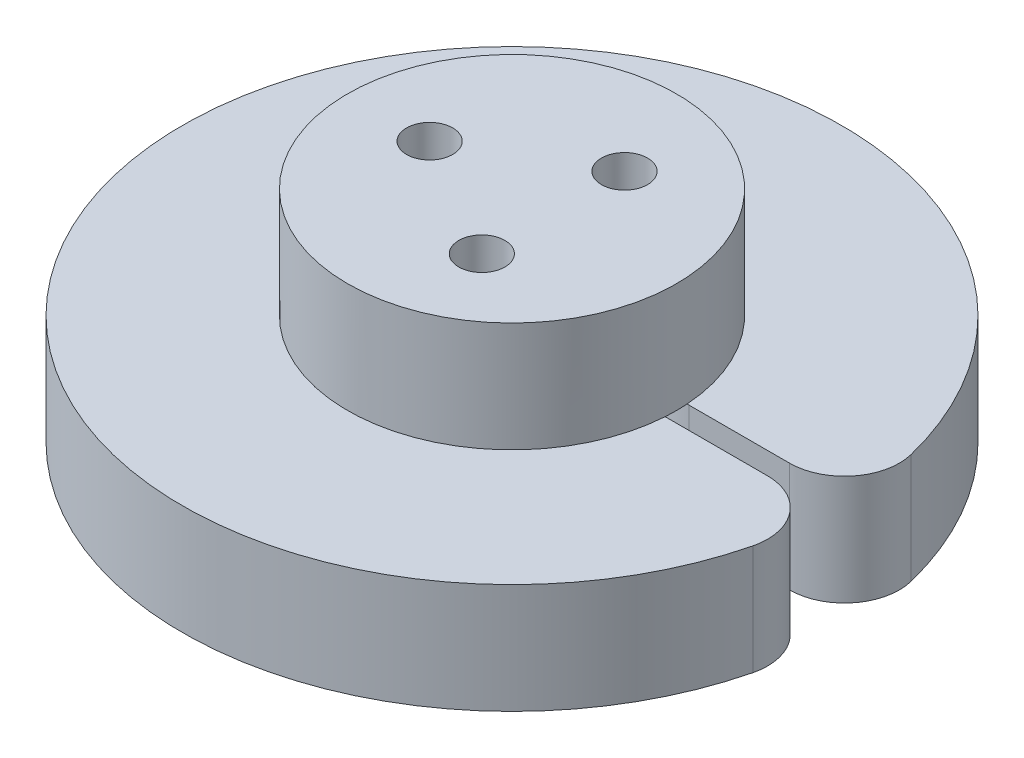
SolidWorks part; units mm, degrees
ref_plane "前视基准面" through (0, 0, 0) normal (0, 0, 1) x (1, 0, 0)
ref_plane "上视基准面" through (0, 0, 0) normal (0, 1, 0) x (1, 0, 0)
ref_plane "右视基准面" through (0, 0, 0) normal (1, 0, 0) x (0, 0, -1)
other "Configuration Table"
sketch "草图1" plane through (0, 0, 0) normal (0, 1, 0) x (1, 0, 0)
  circle A0 centre (0, 0) radius 30
  dimension "D1" = 60
extrude "凸台-拉伸1" add sketch "草图1" along normal blind 10
sketch "草图2" plane through (0, 10, 0) normal (0, 1, 0) x (1, 0, 0)
  circle A0 centre (0, 0) radius 14.975
  dimension "D1" = 29.95
extrude "凸台-拉伸2" add sketch "草图2" along normal blind 10
sketch "草图3" plane through (0, 0, 0) normal (0, -1, 0) x (1, 0, 0)
  circle A0 centre (0, 0) radius 14.975
  dimension "D1" = 29.95
extrude "凸台-拉伸3" add sketch "草图3" along normal blind 6
sketch "草图4" plane through (0, -6, 0) normal (0, -1, 0) x (1, 0, 0)
  circle A0 centre (0, 0) radius 7.5 construction
  circle A1 centre (-7.5, 0) radius 2.1
  circle A2 centre (3.75, 6.4952) radius 2.1
  circle A3 centre (3.75, -6.4952) radius 2.1
  point P11 (0, 0)
  dimension "D1" = 15
  dimension "D2" = 4.2
  dimension "D3" = 3
extrude "切除-拉伸1" cut sketch "草图4" against normal through all
sketch "草图6" plane through (0, 10, 0) normal (0, 1, 0) x (1, 0, 0)
  line L0 (10.9343, 1) -> (10.9343, -1) construction
  line L1 (10.9343, 1) -> (30.9343, 1)
  line L3 (10.9343, -1) -> (30.9343, -1)
  line L4 (30.9343, 1) -> (30.9343, -1)
  arc A0 (10.9343, 1) -> (10.9343, -1) centre (8, 0) ccw
  dimension "D1" = 6.2
  dimension "D2" = 8
  dimension "D3" = 2
  dimension "D4" = 20
extrude "切除-拉伸3" cut sketch "草图6" against normal through all
fillet "圆角1" radius 10 2 edges at (10.9343, 2, -1) (10.9343, 2, 1)
fillet "圆角2" radius 5 2 edges at (29.9833, 5, -1) (29.9833, 5, 1)
fillet "圆角3" radius 0.2 2 edges at (14.9415, -3, 1.0015) (14.9415, -3, -1.0015)
sketch "草图7" plane through (0, 10, 0) normal (0, -1, 0) x (1, 0, 0)
  circle A0 centre (8, 0) radius 1.25
  dimension "D1" = 2.5
extrude "切除-拉伸4" cut sketch "草图7" against normal blind 8
